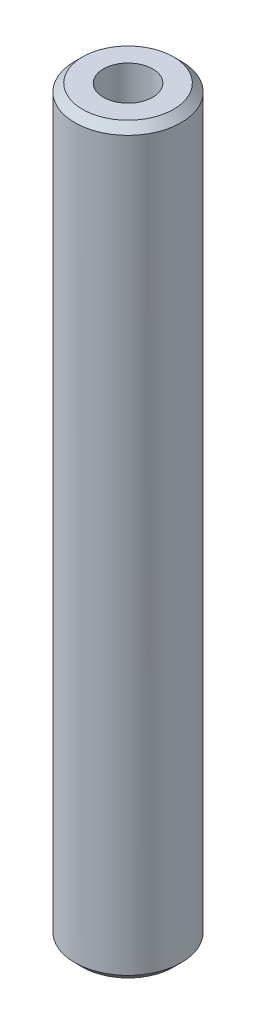
SolidWorks part; units mm, degrees
ref_plane "Front Plane" through (0, 0, 0) normal (0, 0, 1) x (1, 0, 0)
ref_plane "Top Plane" through (0, 0, 0) normal (0, 1, 0) x (1, 0, 0)
ref_plane "Right Plane" through (0, 0, 0) normal (1, 0, 0) x (0, 0, -1)
sketch "Sketch1" plane through (0, 0, 0) normal (0, 1, 0) x (1, 0, 0)
  circle A0 centre (0, 0) radius 5
  dimension "SHAFT_OD" = 10
extrude "Boss-Extrude1" add sketch "Sketch1" along normal blind 69.8446
sketch "Sketch2" plane through (0, 0, 0) normal (0, 1, 0) x (1, 0, 0)
  circle A0 centre (0, 0) radius 2.3158
  dimension "BORE_D" = 4.6316
extrude "Cut-Extrude1" cut sketch "Sketch2" along normal through all
chamfer "Chamfer1" distance 0.7226 angle 45 2 edges at (0, 69.8446, 5) (0, 0, 5)
